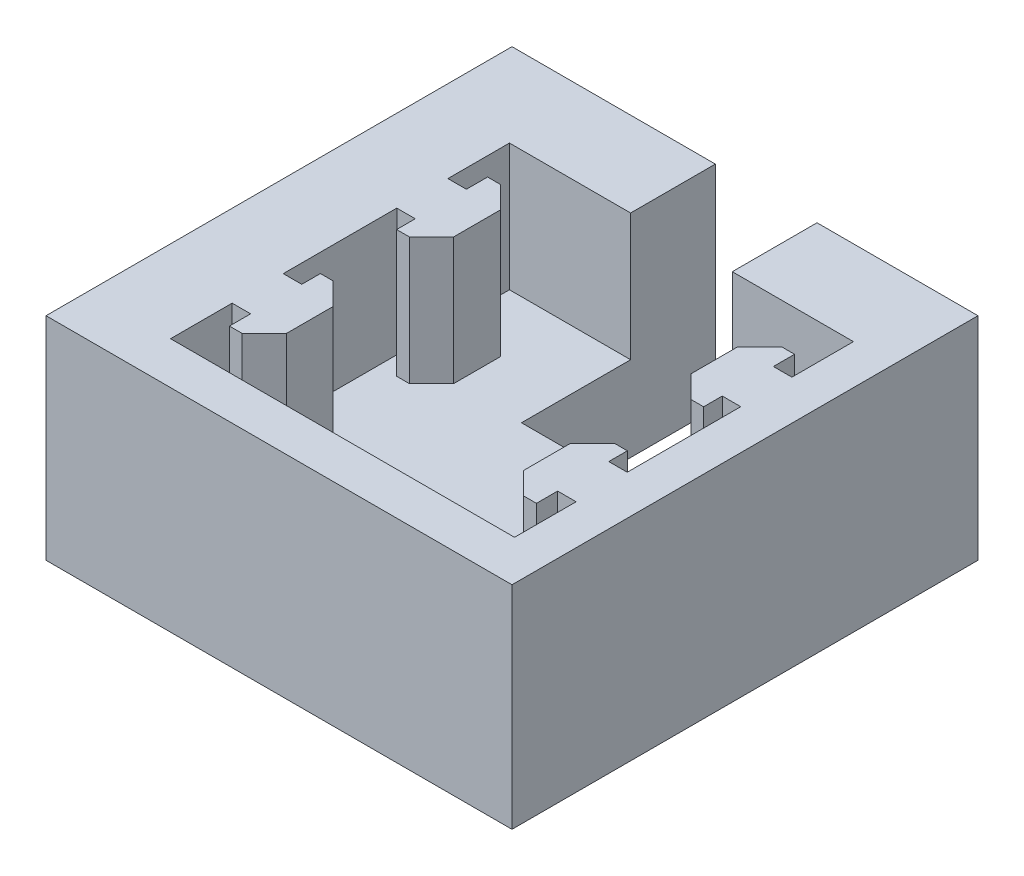
SolidWorks part; units mm, degrees
ref_plane "Front Plane" through (0, 0, 0) normal (0, 0, 1) x (1, 0, 0)
ref_plane "Top Plane" through (0, 0, 0) normal (0, 1, 0) x (1, 0, 0)
ref_plane "Right Plane" through (0, 0, 0) normal (1, 0, 0) x (0, 0, -1)
sketch "Sketch1" plane through (0, 0, 0) normal (0, 1, 0) x (1, 0, 0)
  line L1 (0, 0) -> (-55, 0)
  line L2 (0, 0) -> (0, -55)
  line L3 (0, -55) -> (-55, -55)
  line L4 (-55, 0) -> (-55, -55)
  dimension "D1" = 55
  dimension "D2" = 55
extrude "Boss-Extrude1" add sketch "Sketch1" along normal blind 10
sketch "Sketch2" plane through (0, 10, 0) normal (0, 1, 0) x (1, 0, 0)
  line L0 (-45.3163, -17.2674) -> (-43.1163, -17.2674)
  line L2 (-43.1163, -17.2674) -> (-43.1163, -14.7674)
  line L3 (-43.1163, -14.7674) -> (-41.6163, -14.7674)
  line L4 (-41.6163, -14.7674) -> (-39, -17.3837)
  line L5 (-39, -17.3837) -> (-39, -22.8837)
  line L6 (-39, -22.8837) -> (-41.6163, -25.5)
  line L7 (-41.6163, -25.5) -> (-43.1163, -25.5)
  line L8 (-43.1163, -25.5) -> (-43.1163, -23.3)
  line L9 (-43.1163, -23.3) -> (-45.3163, -23.3)
  line L10 (-45.3163, -23.3) -> (-45.3163, -17.2674)
  line L13 (-25, 0) -> (-25, -55) construction
  line L15 (-55, -30) -> (-3.9273, -30) construction
  line L18 (-6.8837, -23.3) -> (-4.6837, -23.3)
  line L19 (-6.8837, -25.5) -> (-6.8837, -23.3)
  line L20 (-8.3837, -25.5) -> (-6.8837, -25.5)
  line L21 (-11, -22.8837) -> (-8.3837, -25.5)
  line L22 (-11, -17.3837) -> (-11, -22.8837)
  line L23 (-8.3837, -14.7674) -> (-11, -17.3837)
  line L24 (-6.8837, -14.7674) -> (-8.3837, -14.7674)
  line L25 (-6.8837, -17.2674) -> (-6.8837, -14.7674)
  line L26 (-4.6837, -17.2674) -> (-6.8837, -17.2674)
  line L27 (-4.6837, -23.3) -> (-4.6837, -17.2674)
  line L28 (-43.1163, -36.7) -> (-45.3163, -36.7)
  line L29 (-43.1163, -34.5) -> (-43.1163, -36.7)
  line L30 (-41.6163, -34.5) -> (-43.1163, -34.5)
  line L31 (-39, -37.1163) -> (-41.6163, -34.5)
  line L32 (-39, -42.6163) -> (-39, -37.1163)
  line L33 (-41.6163, -45.2326) -> (-39, -42.6163)
  line L34 (-43.1163, -45.2326) -> (-41.6163, -45.2326)
  line L35 (-43.1163, -42.7326) -> (-43.1163, -45.2326)
  line L36 (-45.3163, -42.7326) -> (-43.1163, -42.7326)
  line L37 (-45.3163, -36.7) -> (-45.3163, -42.7326)
  line L38 (-6.8837, -34.5) -> (-6.8837, -36.7)
  line L39 (-8.3837, -34.5) -> (-6.8837, -34.5)
  line L40 (-11, -37.1163) -> (-8.3837, -34.5)
  line L41 (-11, -42.6163) -> (-11, -37.1163)
  line L42 (-8.3837, -45.2326) -> (-11, -42.6163)
  line L43 (-6.8837, -45.2326) -> (-8.3837, -45.2326)
  line L44 (-6.8837, -42.7326) -> (-6.8837, -45.2326)
  line L45 (-4.6837, -42.7326) -> (-6.8837, -42.7326)
  line L46 (-4.6837, -36.7) -> (-4.6837, -42.7326)
  line L47 (-6.8837, -36.7) -> (-4.6837, -36.7)
  line L48 (-55, -55) -> (0, -55) construction
  line L49 (-55, 0) -> (-55, -55) construction
  point P20 (-55, -27.5)
  point P52 (-27.5, -55)
  dimension "D1" = 2.2
  dimension "D2" = 2.2
  dimension "D3" = 2.5
  dimension "D4" = 2.2
  dimension "D5" = 3.7
  dimension "D6" = 3.7
  dimension "D7" = 5.5
  dimension "D8" = 1.5
  dimension "D9" = 1.5
  dimension "D10" = 4.5
  dimension "D11" = 14
  dimension "D12" = 0
  dimension "D13" = 2.5
  dimension "D14" = 2.5
  dimension "D15" = 0
extrude "Boss-Extrude3" add sketch "Sketch2" along normal blind 15
sketch "Sketch3" plane through (0, 10, 0) normal (0, 1, 0) x (1, 0, 0)
  line L0 (0, -55) -> (0, 0) construction
  line L1 (-55, 0) -> (0, 0)
  line L2 (-55, 0) -> (-55, -10)
  line L3 (-55, -10) -> (0, -10)
  line L4 (0, 0) -> (0, -10)
  line L6 (-55, -55) -> (0, -55)
  line L7 (-55, -55) -> (-55, -50)
  line L8 (-55, -50) -> (0, -50)
  line L9 (0, -55) -> (0, -50)
  line L10 (-55, -10) -> (-45.3, -10)
  line L11 (-55, -10) -> (-55, -50)
  line L12 (-55, -50) -> (-45.3, -50)
  line L13 (-45.3, -10) -> (-45.3, -50)
  line L14 (0, -10) -> (-4.7, -10)
  line L15 (0, -10) -> (0, -50)
  line L16 (0, -50) -> (-4.7, -50)
  line L17 (-4.7, -10) -> (-4.7, -50)
  line M15 (-45.3163, -42.7326) -> (-45.3163, -36.7)
  line M17 (-45.3163, -23.3) -> (-45.3163, -17.2674)
  line M27 (0, -55) -> (0, 0)
  line M28 (0, 0) -> (-55, 0)
  line M29 (-55, 0) -> (-55, -55)
  line M30 (-55, -55) -> (0, -55)
  line M39 (-4.6837, -17.2674) -> (-4.6837, -23.3)
  line M44 (-4.6837, -36.7) -> (-4.6837, -42.7326)
  dimension "D1" = 10
  dimension "D2" = 5
  dimension "D3" = 9.7
  dimension "D4" = 4.7
extrude "Boss-Extrude5" add sketch "Sketch3" along normal blind 15 contours L3 M29 M27 M28 | L13 L3 L8 M29 M15 M17 | L8 M29 M30 M27 | L3 L17 L8 M39 M44 M27 | L15 L14 L17 L16 | L2 L1 L4 L3 | L7 L6 L9 L8 | L11 L10 L13 L12 region at (-27.5, 10, 5) region at (-50.15, 10, 30) region at (-2.35, 10, 30) region at (-27.5, 10, 52.5)
sketch "Sketch7" plane through (0, 25, 0) normal (0, 1, 0) x (1, 0, 0)
  line L0 (-25, 0) -> (-25, -53.168) construction
  line L1 (-31, 0) -> (-19, 0)
  line L2 (-31, 0) -> (-31, -22.8837)
  line L3 (-31, -22.8837) -> (-19, -22.8837)
  line L4 (-19, 0) -> (-19, -22.8837)
  line L8 (0, 0) -> (-55, 0) construction
  point P8 (-27.5, 0)
  dimension "D1" = 12
  dimension "D2" = 6
  dimension "D3" = 0
  dimension "D4" = 0
  dimension "D5" = 2.5
  dimension "D6" = 0
extrude "Cut-Extrude3" cut sketch "Sketch7" against normal blind 45
sketch "Sketch8" plane through (0, 0, 0) normal (0, 0, -1) x (-1, 0, 0)
  line L0 (31, 0) -> (55, 0) construction
  line L1 (55, 25) -> (55, 0) construction
  circle A0 centre (50, 9) radius 2
  dimension "D1" = 4
  dimension "D2" = 9
  dimension "D3" = 5
extrude "Cut-Extrude4" cut sketch "Sketch8" against normal blind 7
